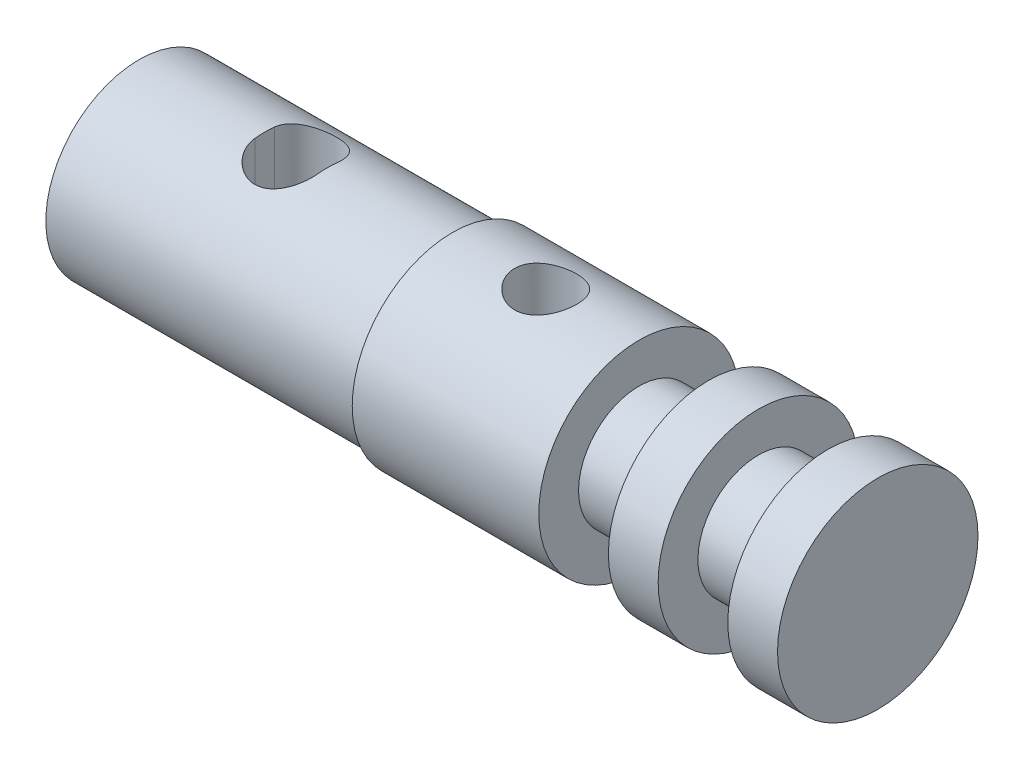
SolidWorks part; units mm, degrees
ref_plane "Front Plane" through (0, 0, 0) normal (0, 0, 1) x (1, 0, 0)
ref_plane "Top Plane" through (0, 0, 0) normal (0, 1, 0) x (1, 0, 0)
ref_plane "Right Plane" through (0, 0, 0) normal (1, 0, 0) x (0, 0, -1)
sketch "Sketch1" plane through (0, 0, 0) normal (0, 0, 1) x (1, 0, 0)
  line L0 (-18.8585, 0) -> (18.8585, 0)
  line L1 (18.8585, 0) -> (18.8585, 5.1181)
  line L2 (18.8585, 5.1181) -> (16.3185, 5.1181)
  line L3 (-2.8585, 5.1181) -> (-2.8585, 4.7625)
  line L4 (-2.8585, 4.7625) -> (-18.8585, 4.7625)
  line L5 (-18.8585, 4.7625) -> (-18.8585, 0)
  line L6 (6.6665, 5.1181) -> (6.6665, 3.0861)
  line L7 (6.6665, 3.0861) -> (10.2225, 3.0861)
  line L8 (10.2225, 3.0861) -> (10.2225, 5.1181)
  line L9 (12.7625, 5.1181) -> (12.7625, 3.0861)
  line L10 (12.7625, 3.0861) -> (16.3185, 3.0861)
  line L11 (16.3185, 3.0861) -> (16.3185, 5.1181)
  line L12 (6.6665, 5.1181) -> (-2.8585, 5.1181)
  line L13 (12.7625, 5.1181) -> (10.2225, 5.1181)
  line L14 (1.904, 5.1181) -> (1.904, 0) construction
  line L15 (0.3165, 5.1181) -> (0.3165, 0) construction
  line L16 (3.4915, 5.1181) -> (3.4915, 0) construction
  point P4 (0, 0)
  dimension "D1" = 5.1181
  dimension "D2" = 3.556
  dimension "D3" = 4.7625
  dimension "D4" = 3.0861
  dimension "D5" = 16
  dimension "D6" = 2.54
  dimension "D9" = 3.175
  dimension "D8" = 1.5875
  dimension "D7" = 1.5875
revolve "Revolve1" add sketch "Sketch1" angle 360 about L0
ref_plane "Plane1" through (0, -5.1181, 0) normal (0, -1, 0) x (-1, 0, 0)
hole_wizard "1/8 (0.125) Diameter Hole1" positions "Sketch2" profile "Sketch3" hole size "1/8" standard "ANSI Inch" end condition through all
sketch "Sketch2" plane through (0, -5.1181, 0) normal (0, -1, 0) x (-1, 0, 0)
  line L0 (-6.6665, 0) -> (2.8585, 0) construction
  line L2 (-6.6665, 5.1181) -> (-6.6665, -5.1181) construction
  line L3 (2.8585, -5.1181) -> (2.8585, 5.1181) construction
  point P0 (-1.904, 0)
sketch "Sketch3" plane through (1.904, -5.1181, 0) normal (1, 0, 0) x (0, 0, -1)
  line L0 (0, 0) -> (0, 10.2362)
  line L1 (0, 10.2362) -> (1.5875, 10.2362)
  line L2 (1.5875, 10.2362) -> (1.5875, 0)
  line L5 (1.5875, 0) -> (0, 0)
  line L11 (0, -6.35) -> (0, 107.95) construction
  dimension "Thru Hole Dia." = 3.175
  dimension "Thru Hole Depth" = 10.2362
hole_wizard "1/8 (0.1250) Dowel Slot1" positions "Sketch4" profile "Sketch5" size "1/8" standard "ANSI Inch" slot yes end condition through all
sketch "Sketch4" plane through (0, -5.1181, 0) normal (0, -1, 0) x (-1, 0, 0)
  line L0 (10.8585, -2.0875) -> (10.8585, 2.0875) construction
  line L1 (0, 0) -> (2.8585, 0) construction
  line L2 (2.8585, 0) -> (18.8585, 0) construction
  line L4 (18.8585, -4.7625) -> (18.8585, 4.7625) construction
  line L5 (2.8585, -5.1181) -> (2.8585, 5.1181) construction
  point P0 (10.8585, 0)
sketch "Sketch5" plane through (-10.8585, -5.1181, 0) normal (1, 0, 0) x (0, 0, -1)
  line L0 (0, 0) -> (0, 10.2362)
  line L1 (0, 10.2362) -> (1.5875, 10.2362)
  line L2 (1.5875, 10.2362) -> (1.5875, 0)
  line L5 (1.5875, 0) -> (0, 0)
  line L11 (0, -6.35) -> (0, 107.95) construction
  dimension "Thru Hole Dia." = 3.175
  dimension "Thru Hole Depth" = 10.2362
ref_axis "Axis1" through (-18.8585, 0, 0) along (1, 0, 0)
